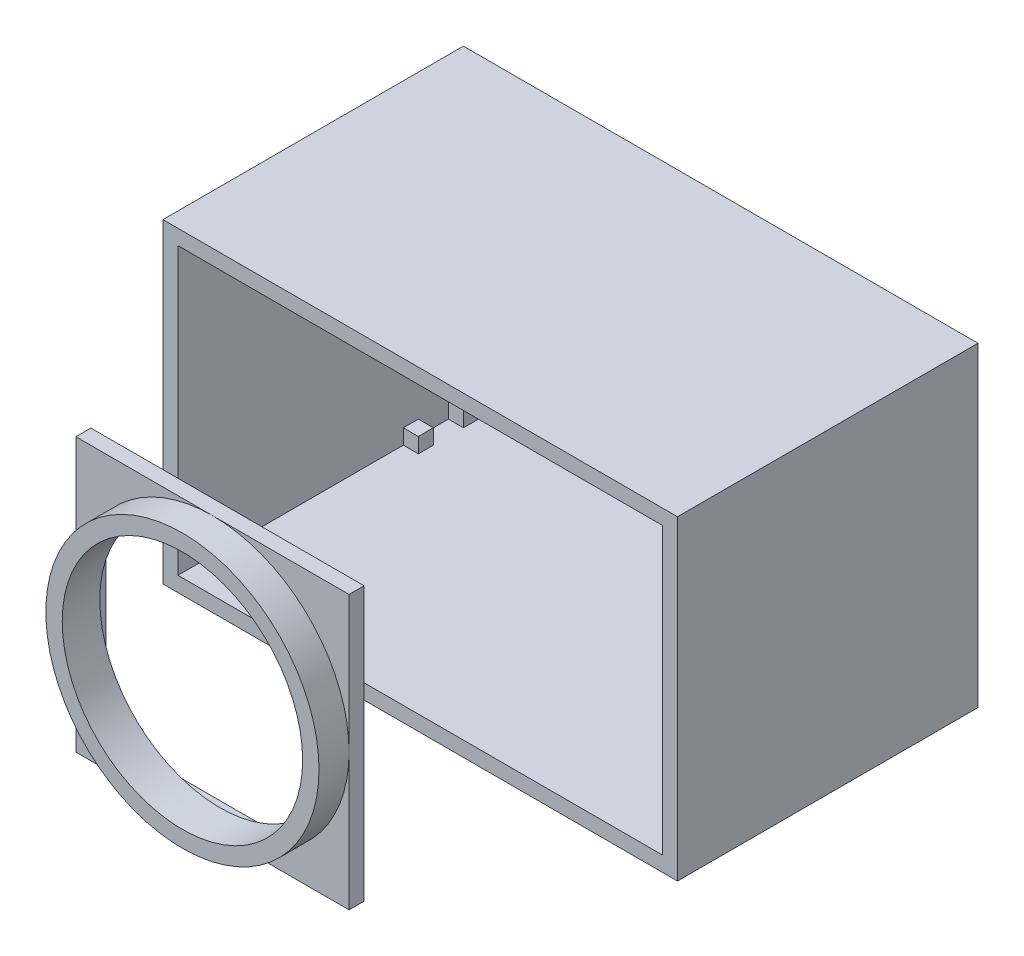
SolidWorks part; units mm, degrees
note: The reader was unsure of these and kept them because the rebuilt part matched: shared geometry of "Sketch1<2>".
ref_plane "Front Plane" through (0, 0, 0) normal (0, 0, 1) x (1, 0, 0)
ref_plane "Top Plane" through (0, 0, 0) normal (0, 1, 0) x (1, 0, 0)
ref_plane "Right Plane" through (0, 0, 0) normal (1, 0, 0) x (0, 0, -1)
sketch "Sketch1" plane through (0, 0, 0) normal (0, 0, 1) x (1, 0, 0)
  line L1 (0, 0) -> (434.975, 0)
  line L2 (0, 0) -> (0, 266.7)
  line L3 (0, 266.7) -> (434.975, 266.7)
  line L4 (434.975, 0) -> (434.975, 266.7)
  line L5 (12.7, 12.7) -> (422.275, 12.7)
  line L6 (12.7, 12.7) -> (12.7, 254)
  line L7 (12.7, 254) -> (422.275, 254)
  line L8 (422.275, 12.7) -> (422.275, 254)
  dimension "D1" = 409.575
  dimension "D2" = 241.3
  dimension "D3" = 12.7
  dimension "D4" = 12.7
  dimension "D5" = 12.7
  dimension "D6" = 12.7
extrude "Boss-Extrude1" add sketch "Sketch1" along normal blind 203.2
ref_plane "Plane1" through (0, 0, 381) normal (0, 0, 1) x (1, 0, 0)
sketch "Sketch2" plane through (0, 0, 381) normal (0, 0, 1) x (1, 0, 0)
  line L0 (422.275, 254) -> (12.7, 254) construction
  line L1 (12.7, 254) -> (12.7, 12.7) construction
  circle A0 centre (219.71, 133.35) radius 101.6
  circle A1 centre (219.71, 133.35) radius 115.4513
  point P2 (0, 0)
  point P10 (219.71, 248.8013)
  point P13 (104.2587, 133.35)
  point P14 (104.2587, 133.35)
  point P15 (104.2587, 133.35)
  point P16 (335.1613, 133.35)
  point P19 (219.71, 17.8987)
  point P22 (335.1613, 133.35)
  point P23 (0, 0)
  point P24 (0, 0)
  dimension "D1" = 207.01
  dimension "D2" = 120.65
extrude "Boss-Extrude3" add sketch "Sketch2" along normal blind 25.4 separate body
sketch "Sketch4" plane through (0, 0, 381) normal (0, 0, 1) x (1, 0, 0)
  line L1 (104.2587, 248.8013) -> (335.1613, 248.8013)
  line L2 (104.2587, 248.8013) -> (104.2587, 17.8987)
  line L3 (104.2587, 17.8987) -> (335.1613, 17.8987)
  line L4 (335.1613, 248.8013) -> (335.1613, 17.8987)
  circle A0 centre (219.71, 133.35) radius 101.6
  circle A1 centre (219.71, 133.35) radius 115.4513 construction
  point P6 (219.71, 248.8013)
  point P7 (219.71, 248.8013)
  point P8 (104.2587, 133.35)
  point P9 (335.1613, 133.35)
  point P10 (219.71, 17.8987)
  point P11 (219.71, 133.35)
extrude "Boss-Extrude4" add sketch "Sketch4" against normal blind 12.7
sketch "Sketch8" plane through (0, 0, 368.3) normal (0, 0, -1) x (-1, 0, 0)
  line L0 (-335.1613, 17.8987) -> (-335.1613, 248.8013) construction
  line L1 (-322.4613, 236.1013) -> (-116.9587, 236.1013)
  line L2 (-322.4613, 236.1013) -> (-322.4613, 30.5987)
  line L3 (-322.4613, 30.5987) -> (-116.9587, 30.5987)
  line L4 (-116.9587, 236.1013) -> (-116.9587, 30.5987)
  line L5 (-322.4613, 236.1013) -> (-116.9587, 30.5987) construction
  line L6 (-322.4613, 30.5987) -> (-116.9587, 236.1013) construction
  line L7 (-335.1613, 248.8013) -> (-104.2587, 248.8013) construction
  line L8 (-104.2587, 248.8013) -> (-104.2587, 17.8987) construction
  line L9 (-104.2587, 17.8987) -> (-335.1613, 17.8987) construction
  point P4 (-219.71, 133.35)
  point P13 (0, 0)
  dimension "D1" = 12.7
  dimension "D2" = 12.7
  dimension "D3" = 12.7
  dimension "D4" = 12.7
sketch3d "3DSketch2"
  line L0 (422.275, 254, 203.2) -> (322.4613, 236.1013, 368.3)
  line L1 (434.975, 266.7, 203.2) -> (335.1613, 248.8013, 368.3)
  line L2 (422.275, 12.7, 203.2) -> (322.4613, 30.5987, 368.3)
  line L3 (434.975, 0, 203.2) -> (335.1613, 17.8987, 368.3)
extrude "Cut-Extrude1" cut sketch "Sketch8" against normal blind 6.35
other "Boundary-Surface2"
other "Boundary-Surface3"
other "Boundary-Surface4"
other "Boundary-Surface5"
other "Boundary-Surface6"
other "Boundary-Surface7"
other "Boundary-Surface8"
other "Boundary-Surface9"
sketch "Sketch10" plane through (0, 0, 0) normal (0, 0, 1) x (1, 0, 0)
  line L0 (422.275, 254) -> (12.7, 254) construction
  line L1 (409.575, 254) -> (422.275, 254)
  line L2 (409.575, 254) -> (409.575, 241.3)
  line L3 (409.575, 241.3) -> (422.275, 241.3)
  line L4 (422.275, 254) -> (422.275, 241.3)
  line L5 (409.575, 254) -> (422.275, 241.3) construction
  line L6 (409.575, 241.3) -> (422.275, 254) construction
  line L7 (422.275, 12.7) -> (422.275, 254) construction
  line L8 (12.7, 254) -> (12.7, 241.3)
  line L9 (12.7, 254) -> (25.4, 254)
  line L10 (25.4, 254) -> (25.4, 241.3)
  line L11 (12.7, 241.3) -> (25.4, 241.3)
  line L12 (12.7, 25.4) -> (12.7, 12.7)
  line L13 (12.7, 25.4) -> (25.4, 25.4)
  line L14 (25.4, 25.4) -> (25.4, 12.7)
  line L15 (12.7, 12.7) -> (25.4, 12.7)
  line L16 (409.575, 25.4) -> (409.575, 12.7)
  line L17 (409.575, 25.4) -> (422.275, 25.4)
  line L18 (422.275, 25.4) -> (422.275, 12.7)
  line L19 (409.575, 12.7) -> (422.275, 12.7)
  line L20 (409.575, 254) -> (409.575, 25.4) construction
  point P4 (415.925, 247.65)
  dimension "D1" = 12.7
  dimension "D2" = 12.7
  dimension "D5" = 228.6
  dimension "D3" = 2
  dimension "D4" = 2
extrude "Boss-Extrude5" add sketch "Sketch10" along normal blind 12.7
extrude "Boss-Extrude6" add sketch "Sketch1<2>" against normal blind 50.8
sketch "Sketch1<2>" plane through (0, 0, 0) normal (0, 0, 1) x (1, 0, 0) same geometry as "Sketch1"
pattern_linear "LPattern1" count 2 spacing 38.1 along (0, 0, -1) of "Boss-Extrude5"
